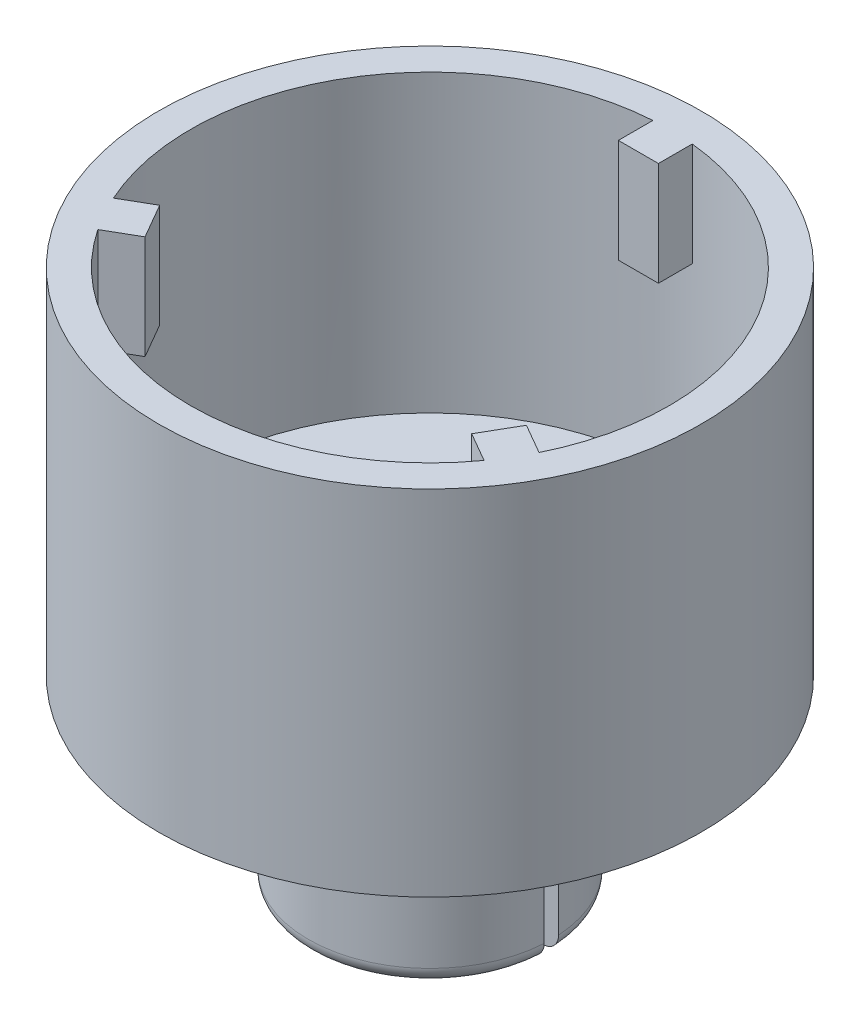
SolidWorks part; units mm, degrees
ref_plane "Front Plane" through (0, 0, 0) normal (0, 0, 1) x (1, 0, 0)
ref_plane "Top Plane" through (0, 0, 0) normal (0, 1, 0) x (1, 0, 0)
ref_plane "Right Plane" through (0, 0, 0) normal (1, 0, 0) x (0, 0, -1)
sketch "Sketch1" plane through (0, 0, 0) normal (0, 1, 0) x (1, 0, 0)
  circle A0 centre (0, 0) radius 34
  dimension "D1" = 68
extrude "Boss-Extrude1" add sketch "Sketch1" along normal blind 44.3
sketch "Sketch2" plane through (0, 44.3, 0) normal (0, 1, 0) x (1, 0, 0)
  circle A0 centre (0, 0) radius 30
  dimension "D1" = 60
extrude "Cut-Extrude1" cut sketch "Sketch2" against normal blind 37
sketch "Sketch3" plane through (0, 0, 0) normal (0, -1, 0) x (1, 0, 0)
  circle A0 centre (0, 0) radius 19.5
  dimension "D1" = 39
extrude "Boss-Extrude2" add sketch "Sketch3" along normal blind 7
sketch "Sketch4" plane through (0, -7, 0) normal (0, -1, 0) x (1, 0, 0)
  circle A0 centre (0, 0) radius 15.25
  dimension "D1" = 30.5
extrude "Boss-Extrude3" add sketch "Sketch4" along normal blind 16
fillet "Fillet1" radius 5 1 edges at (0, 0, -19.5)
sketch "Sketch5" plane through (0, 44.3, 0) normal (0, 1, 0) x (1, 0, 0)
  line L0 (-1.9905, 29.9339) -> (-1.9905, 25.6053)
  line L1 (-1.9905, 25.6053) -> (3.0302, 25.6053)
  line L2 (3.0302, 25.6053) -> (3.0302, 29.8466)
  line L3 (26.9188, -13.2431) -> (23.1701, -11.0788)
  line L4 (23.1701, -11.0788) -> (20.6597, -15.4269)
  line L5 (20.6597, -15.4269) -> (24.3328, -17.5475)
  line L6 (-24.9282, -16.6908) -> (-21.1796, -14.5265)
  line L7 (-21.1796, -14.5265) -> (-23.69, -10.1784)
  line L8 (-23.69, -10.1784) -> (-27.363, -12.299)
  circle A0 centre (0, 0) radius 30 construction
  arc A1 (24.3328, -17.5475) -> (26.9188, -13.2431) centre (0, 0) ccw
  circle A2 centre (0, 0) radius 30
  arc A3 (3.0302, 29.8466) -> (-1.9905, 29.9339) centre (0, 0) ccw
  arc A4 (-27.363, -12.299) -> (-24.9282, -16.6908) centre (0, 0) ccw
  point P19 (0, 0)
  dimension "D1" = 0
  dimension "D2" = 3
extrude "Boss-Extrude4" add sketch "Sketch5" against normal blind 13
sketch "Sketch7" plane through (0, -23, 0) normal (0, -1, 0) x (1, 0, 0)
  line L1 (33.0968, 0.9034) -> (-33.0968, 0.9034)
  line L2 (33.0968, 0.9034) -> (33.0968, -0.9034)
  line L3 (33.0968, -0.9034) -> (-33.0968, -0.9034)
  line L4 (-33.0968, 0.9034) -> (-33.0968, -0.9034)
  line L5 (33.0968, 0.9034) -> (-33.0968, -0.9034) construction
  line L6 (33.0968, -0.9034) -> (-33.0968, 0.9034) construction
  point P0 (0, 0)
extrude "Cut-Extrude2" cut sketch "Sketch7" against normal up to surface (16 mm away) up to face at (0, -7, -15.25)
fillet "Fillet2" radius 2 2 edges at (0, -23, 15.25) (0, -23, -15.25)
sketch "Sketch8" plane through (0, 7.3, 0) normal (0, 1, 0) x (1, 0, 0)
  circle A0 centre (0, 0) radius 10.3601
